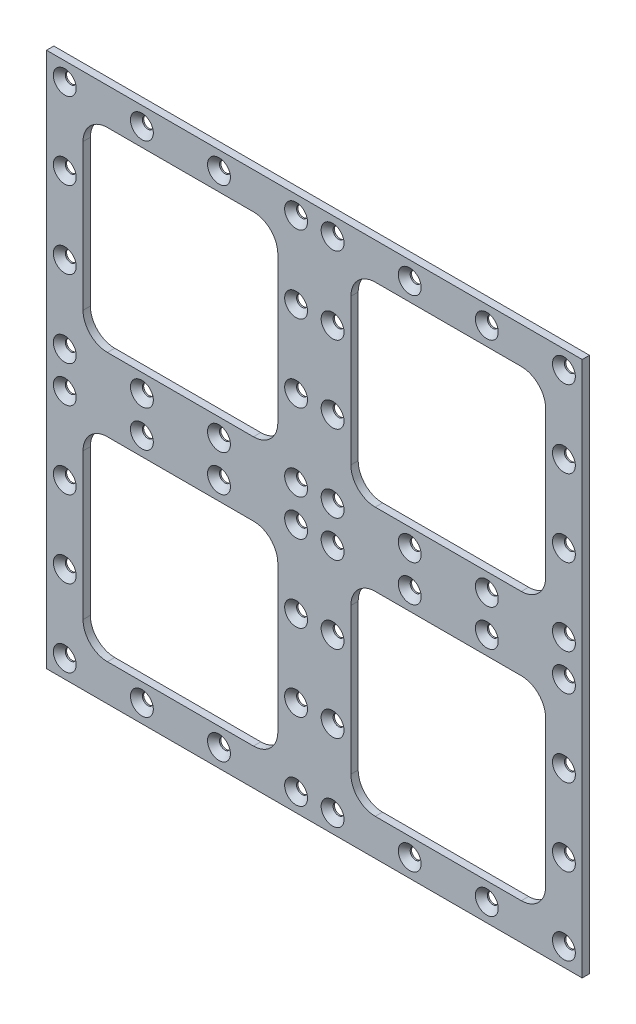
SolidWorks part; units mm, degrees
material "6061-T6 (SS)"
ref_plane "Alzado" through (0, 0, 0) normal (0, 0, 1) x (1, 0, 0)
ref_plane "Planta" through (0, 0, 0) normal (0, 1, 0) x (1, 0, 0)
ref_plane "Vista lateral" through (0, 0, 0) normal (1, 0, 0) x (0, 0, -1)
sketch "Sketch1" plane through (0, 0, 0) normal (0, 0, 1) x (1, 0, 0)
  line L1 (-110, 110) -> (110, 110)
  line L2 (-110, 110) -> (-110, -110)
  line L3 (-110, -110) -> (110, -110)
  line L4 (110, 110) -> (110, -110)
  line L5 (-110, 110) -> (110, -110) construction
  line L6 (-110, -110) -> (110, 110) construction
  point P0 (0, 0)
  dimension "D1" = 220
  dimension "D2" = 220
extrude "Boss-Extrude1" add sketch "Sketch1" along normal blind 3
sketch "Sketch2" plane through (0, 0, 0) normal (0, 0, 1) x (1, 0, 0)
  line L0 (-110, 110) -> (-110, -110) construction
  line L1 (-95, 95) -> (-15, 95)
  line L2 (-95, 95) -> (-95, 15)
  line L3 (-95, 15) -> (-15, 15)
  line L4 (-15, 95) -> (-15, 15)
  line L5 (-95, 95) -> (-15, 15) construction
  line L6 (-95, 15) -> (-15, 95) construction
  line L7 (110, 110) -> (-110, 110) construction
  point P0 (-55, 55)
  point P9 (-55, 95)
  dimension "D1" = 80
  dimension "D2" = 80
  dimension "D3" = 15
  dimension "D4" = 15
extrude "Cut-Extrude2" cut sketch "Sketch2" along normal through all
fillet "Fillet1" radius 10 4 edges at (-95, 95, 1.5) (-15, 95, 1.5) (-15, 15, 1.5) (-95, 15, 1.5)
pattern_linear "LPattern2" count 2 spacing 110 along (0, -1, 0) count 2 spacing 110 along (1, 0, 0) of "Fillet1", "Cut-Extrude2"
sketch "Sketch11" plane through (0, 0, 3) normal (0, 0, 1) x (1, 0, 0)
  line L0 (-110, 110) -> (-110, -110) construction
  line L1 (110, 110) -> (-110, 110) construction
  point P0 (-102.5, 102.5)
  dimension "D1" = 7.5
  dimension "D2" = 7.5
hole_wizard "CSK for M4 Flat Head Machine Screw4" positions "Sketch11" profile "Sketch12" countersink size "M4" standard "ANSI Metric" end condition through all
sketch "Sketch12" plane through (-102.5, 102.5, 3) normal (1, 0, 0) x (0, -1, 0)
  line L0 (0, 0) -> (0, 3)
  line L1 (0, 3) -> (2.25, 3)
  line L2 (2.25, 3) -> (2.25, 2.45)
  line L3 (2.25, 2.45) -> (4.7, 0)
  line L5 (4.7, 0) -> (0, 0)
  line L6 (-2.25, 2.45) -> (-4.7, 0) construction
  line L11 (0, -6.35) -> (0, 107.95) construction
  dimension "Thru Hole Dia." = 4.5
  dimension "Thru Hole Depth" = 3
  dimension "Near C'Sink Dia." = 9.4
  dimension "Near C'Sink Angle" = 90
sketch "Sketch13" plane through (0, 0, 3) normal (0, 0, 1) x (1, 0, 0)
  line L0 (0, 110) -> (0, -110) construction
  line L1 (110, 110) -> (-110, 110) construction
  line L2 (-110, -110) -> (110, -110) construction
  line L3 (-110, 0) -> (110, 0) construction
  line L4 (-110, 110) -> (-110, -110) construction
  line L5 (110, -110) -> (110, 110) construction
pattern_linear "LPattern8" count 4 spacing 31.6667 along (1, 0, 0) count 4 spacing 31.6667 along (0, -1, 0) skipping (1, 1), (1, 2), (2, 1), (2, 2) of "CSK for M4 Flat Head Machine Screw4"
mirror "Mirror1" about plane through (0, 0, 0) normal (1, 0, 0) of "LPattern8" second plane through (0, 0, 0) second plane normal (0, 1, 0)
